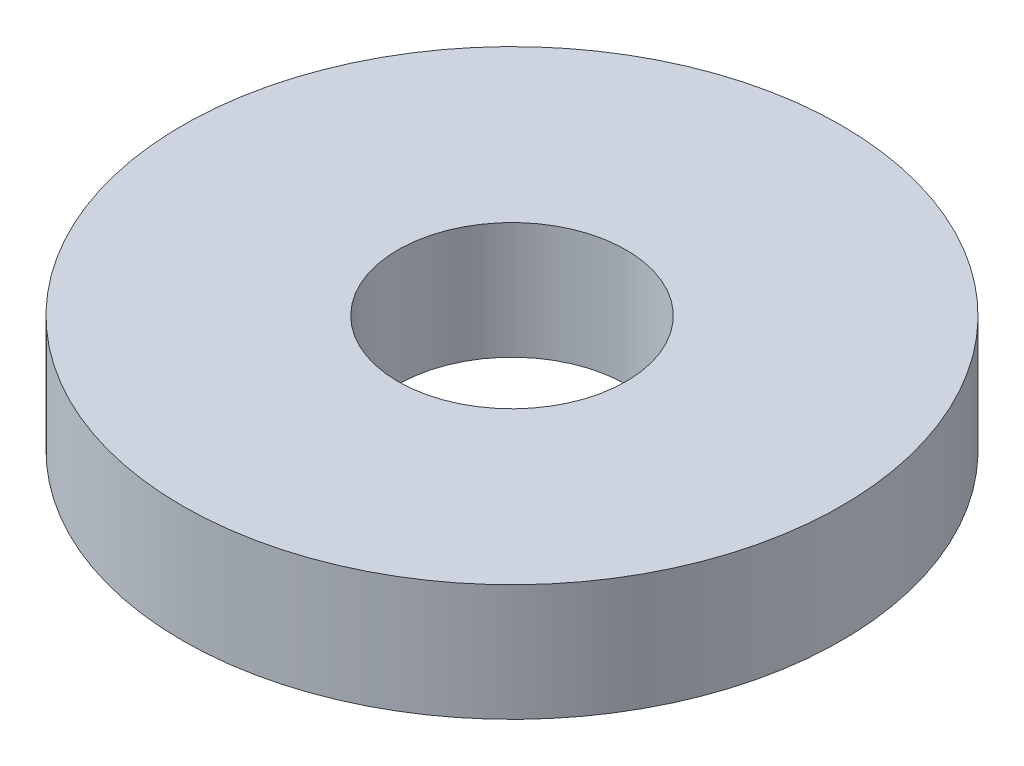
SolidWorks part; units mm, degrees
ref_plane "Front Plane" through (0, 0, 0) normal (0, 0, 1) x (1, 0, 0)
ref_plane "Top Plane" through (0, 0, 0) normal (0, 1, 0) x (1, 0, 0)
ref_plane "Right Plane" through (0, 0, 0) normal (1, 0, 0) x (0, 0, -1)
sketch "Sketch1" plane through (0, 0, 0) normal (0, 1, 0) x (1, 0, 0)
  circle A0 centre (0, 0) radius 65
  dimension "FLANGE_OD" = 130
extrude "Boss-Extrude1" add sketch "Sketch1" along normal blind 23
sketch "Sketch2" plane through (0, 0, 0) normal (0, 1, 0) x (1, 0, 0)
  circle A0 centre (0, 0) radius 22.5
  dimension "BORE_D" = 45
extrude "Cut-Extrude1" cut sketch "Sketch2" along normal through all
sketch "Sketch3" plane through (0, 23, 0) normal (0, 1, 0) x (1, 0, 0)
  circle A0 centre (0, 0) radius 14.3144 construction
  circle A1 centre (-14.3144, 0) radius 4.1757
  dimension "BOLT_D" = 8.3514
  dimension "BOLT_PCD" = 28.6289
extrude "Cut-Extrude2" cut sketch "Sketch3" against normal blind 15.6976 rebuild error yes
pattern_circular "CirPattern1" count 4 over 360 rebuild error yes
